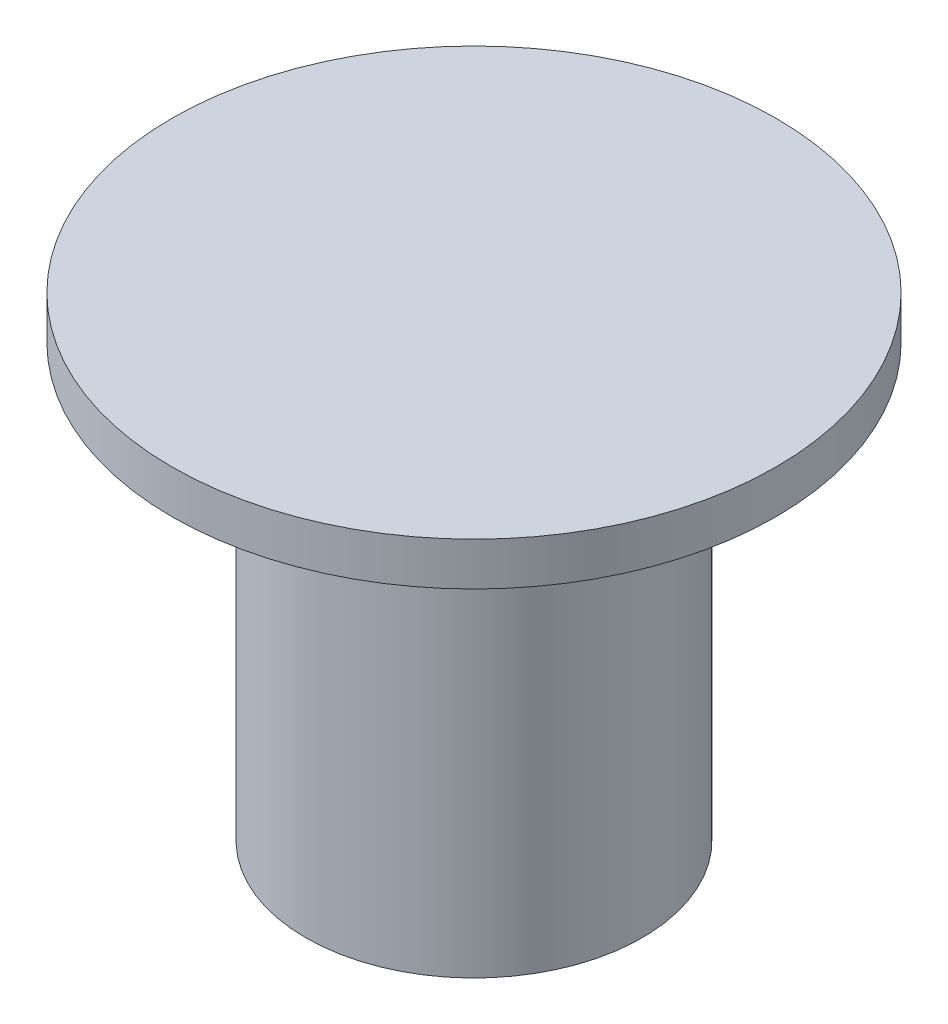
SolidWorks part; units mm, degrees
ref_plane "Plan de face" through (0, 0, 0) normal (0, 0, 1) x (1, 0, 0)
ref_plane "Plan de dessus" through (0, 0, 0) normal (0, 1, 0) x (1, 0, 0)
ref_plane "Plan de droite" through (0, 0, 0) normal (1, 0, 0) x (0, 0, -1)
sketch "Esquisse1" plane through (0, 0, 0) normal (0, 0, 1) x (1, 0, 0)
  line L0 (0, 0) -> (3.5, 0)
  line L1 (3.5, 0) -> (3.5, -0.5)
  line L2 (3.5, -0.5) -> (1.95, -0.5)
  line L3 (1.95, -0.5) -> (1.95, -5.5)
  line L4 (1.95, -5.5) -> (1.45, -5.5)
  line L5 (1.45, -5.5) -> (1.45, -0.5)
  line L6 (1.45, -0.5) -> (0, -0.5)
  line L7 (0, -0.5) -> (0, 0) construction
  line L8 (0, 0) -> (0, -0.5)
  dimension "D1" = 5
  dimension "D2" = 3.5
  dimension "D3" = 1.45
  dimension "D4" = 0.5
  dimension "D5" = 0.5
revolve "Révolution1" add sketch "Esquisse1" angle 360 about L7
sketch "Esquisse3" plane through (0, 0, 0) normal (0, 0, 1) x (1, 0, 0)
  line L0 (1.45, -0.455) -> (1.55, -0.5)
  line L1 (-3.5, -0.5) -> (3.5, -0.5) construction
  line L2 (1.55, -0.5) -> (1.45, -0.5) construction
  line L5 (1.45, -0.545) -> (1.45, -0.455)
  line L7 (1.45, -0.545) -> (1.55, -0.5)
  dimension "D1" = 1.45
  dimension "D2" = 0.045
  dimension "D3" = 0.1
sketch "Esquisse4" plane through (0, -0.5, 0) normal (0, -1, 0) x (-1, 0, 0)
  circle A0 centre (0, 0) radius 1.45
  circle A1 centre (0, 0) radius 1.45 construction
curve "Hélice/Spirale1" pitch 0.2 height 6 turns 30
sweep "Enlèvement de matière-Balayage1" cut profiles "Esquisse3" path "Hélice/Spirale1"
